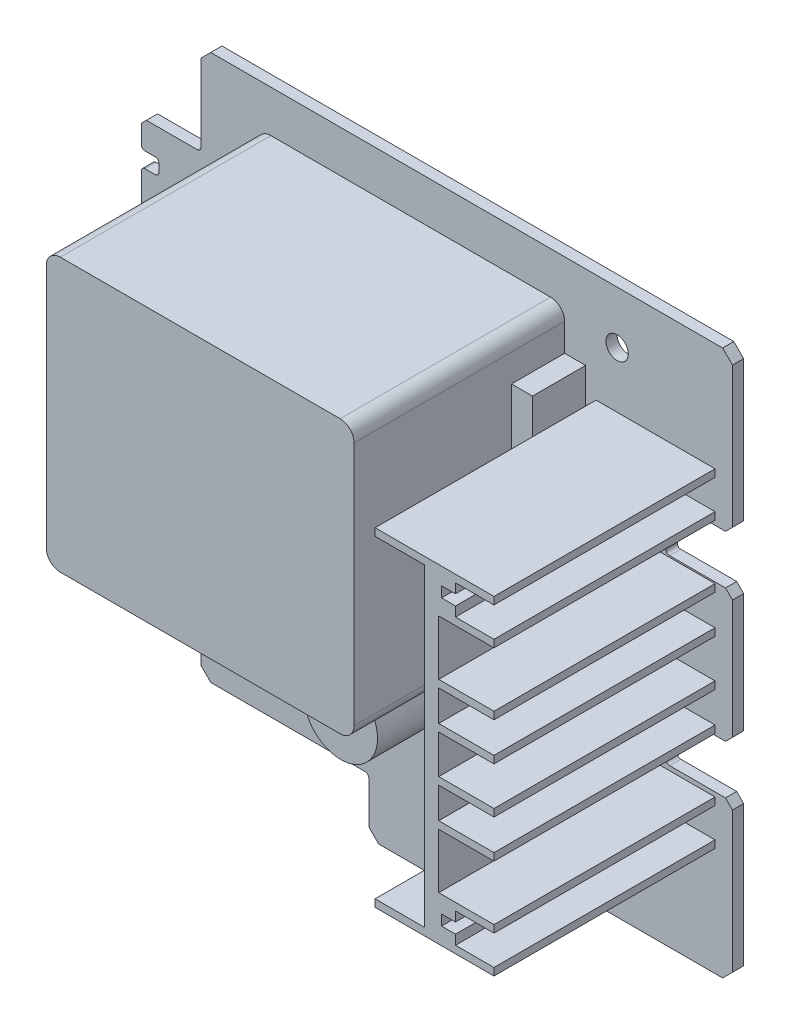
SolidWorks part; units mm, degrees
ref_plane "Front Plane" through (0, 0, 0) normal (0, 0, 1) x (1, 0, 0)
ref_plane "Top Plane" through (0, 0, 0) normal (0, 1, 0) x (1, 0, 0)
ref_plane "Right Plane" through (0, 0, 0) normal (1, 0, 0) x (0, 0, -1)
sketch "Sketch1" plane through (0, 0, 0) normal (0, 0, 1) x (1, 0, 0)
  line L0 (-45.5, -26) -> (-45.5, -13.8)
  line L1 (-45.5, -13.8) -> (-42.5, -13.8)
  line L2 (-42.5, -13.8) -> (-42.5, -8.5)
  line L3 (-42.5, -8.5) -> (-44.5, -8.5)
  line L4 (-44.5, -8.5) -> (-44.5, 8.5)
  line L5 (-44.5, 8.5) -> (-42.5, 8.5)
  line L6 (-42.5, 8.5) -> (-42.5, 13.8)
  line L7 (-42.5, 13.8) -> (-45.5, 13.8)
  line L8 (-45.5, 13.8) -> (-45.5, 19.9)
  line L9 (-45.5, 19.9) -> (-43, 19.9)
  line L10 (-43, 19.9) -> (-43, 22.1)
  line L11 (-43, 22.1) -> (-45.5, 22.1)
  line L12 (-45.5, 22.1) -> (-45.5, 25.2929)
  line L13 (-45.5, 25.2929) -> (-44.7929, 26)
  line L14 (-44.7929, 26) -> (-37, 26)
  line L15 (-37, 26) -> (-37, 37.5858)
  line L16 (-37, 37.5858) -> (-35.5858, 39)
  line L17 (-35.5858, 39) -> (37.5858, 39)
  line L18 (37.5858, 39) -> (39, 37.5858)
  line L19 (39, 37.5858) -> (39, 16.5)
  line L20 (39, 16.5) -> (29.5, 16.5)
  line L21 (29.5, 16.5) -> (29.5, 9.5)
  line L22 (29.5, 9.5) -> (39, 9.5)
  line L23 (39, 9.5) -> (39, -9.5)
  line L24 (39, -9.5) -> (29.5, -9.5)
  line L25 (29.5, -9.5) -> (29.5, -16.5)
  line L26 (29.5, -16.5) -> (39, -16.5)
  line L27 (39, -16.5) -> (39, -37.5858)
  line L28 (39, -37.5858) -> (37.5858, -39)
  line L29 (37.5858, -39) -> (13, -39)
  line L30 (13, -39) -> (13, -45.5858)
  line L31 (13, -45.5858) -> (11.5858, -47)
  line L32 (11.5858, -47) -> (-11.5858, -47)
  line L33 (-11.5858, -47) -> (-13, -45.5858)
  line L34 (-13, -45.5858) -> (-13, -39)
  line L35 (-13, -39) -> (-35.5858, -39)
  line L36 (-35.5858, -39) -> (-37, -37.5858)
  line L37 (-37, -37.5858) -> (-37, -26)
  line L38 (-37, -26) -> (-45.5, -26)
  line L39 (-44.5, 0) -> (0, 0) construction
  line L40 (0, -47) -> (0, 0) construction
  circle A0 centre (-40.5, -21) radius 1.6
  circle A1 centre (22.5, 31.5) radius 1.6
  circle A2 centre (22.5, -31.5) radius 1.6
  dimension "D1" = 3.2
  dimension "D2" = 63
  dimension "D3" = 60
  dimension "D4" = 63
  dimension "D5" = 63
  dimension "D6" = 7.5
  dimension "D7" = 78
  dimension "D8" = 13
  dimension "D9" = 8.5
  dimension "D10" = 86
  dimension "D11" = 5.3
  dimension "D12" = 3
  dimension "D13" = 2.2
  dimension "D14" = 2.5
  dimension "D15" = 58.5
  dimension "D16" = 32.5
  dimension "D17" = 65
  dimension "D18" = 16.9
  dimension "D19" = 25.2
  dimension "D20" = 47.5
  dimension "D21" = 135
  dimension "D22" = 1
  dimension "D23" = 84.5
  dimension "D24" = 135
  dimension "D25" = 2
  dimension "D26" = 8.5
  dimension "D27" = 7
  dimension "D28" = 19
  dimension "D29" = 22.5
  dimension "D30" = 9.5
  dimension "D31" = 2
  dimension "D32" = 135
  dimension "D33" = 135
  dimension "D34" = 135
  dimension "D35" = 5
extrude "Boss-Extrude1" add sketch "Sketch1" along normal blind 1.6
chamfer "Chamfer1" distance 2 angle 45 1 edges at (-45.5, -26, 0.8)
chamfer "Chamfer2" distance 1 angle 45 4 edges at (39, 16.5, 0.8) (39, 9.5, 0.8) (39, -16.5, 0.8) (39, -9.5, 0.8)
fillet "Fillet1" radius 0.5 20 edges at (-45.5, 19.9, 0.8) (-45.5, 22.1, 0.8) (-45.5, 13.8, 0.8) (-44.5, 8.5, 0.8) (-45.5, -13.8, 0.8) (-44.5, -8.5, 0.8) (-37, 26, 0.8) (29.5, 16.5, 0.8) (29.5, 9.5, 0.8) (29.5, -9.5, 0.8) (29.5, -16.5, 0.8) (13, -39, 0.8) (-13, -39, 0.8) (-37, -26, 0.8) (-43, 19.9, 0.8) (-43, 22.1, 0.8) (-42.5, 13.8, 0.8) (-42.5, 8.5, 0.8) (-42.5, -13.8, 0.8) (-42.5, -8.5, 0.8)
sketch "Sketch2" plane through (0, 0, 1.6) normal (0, 0, 1) x (1, 0, 0)
  line L2 (36.5, 17.13) -> (28.6, 17.13)
  line L3 (28.6, 17.13) -> (28.6, 9.28)
  line L4 (28.6, 9.28) -> (36.5, 9.28)
  line L7 (36.5, -9.28) -> (28.6, -9.28)
  line L8 (28.6, -9.28) -> (28.6, -17.13)
  line L9 (28.6, -17.13) -> (36.5, -17.13)
  line L11 (36.5, -23.5) -> (19.5, -23.5)
  line L13 (19.5, 23.5) -> (36.5, 23.5)
  line L18 (39, 17.5) -> (39, 37.5858) construction
  line L19 (15, 27.05) -> (18, 27.05)
  line L20 (-29, 33) -> (15, 33)
  line L21 (-29, 33) -> (-29, -6)
  line L22 (-29, -6) -> (15, -6)
  line L23 (15, 33) -> (15, -6)
  line L24 (18, 27.05) -> (18, -0.05)
  line L25 (18, -0.05) -> (15, -0.05)
  line L26 (18, 13.5) -> (15, 13.5) construction
  line L27 (39, -37.5858) -> (39, -17.5) construction
  line L28 (10.5, -20) -> (15.5, -20)
  line L29 (10.5, -20) -> (10.5, -6)
  line L30 (10.5, -6) -> (15.5, -6)
  line L31 (15.5, -20) -> (15.5, -6)
  line L32 (2.5, -22.5) -> (11.5, -22.5)
  line L33 (2.5, -22.5) -> (2.5, -26.5)
  line L34 (2.5, -26.5) -> (11.5, -26.5)
  line L35 (11.5, -22.5) -> (11.5, -26.5)
  line L36 (-11.5858, -47) -> (11.5858, -47) construction
  line L37 (13.5, -39) -> (37.5858, -39) construction
  line L38 (37.5858, 39) -> (-35.5858, 39) construction
  line L39 (36.5, -22.44) -> (31, -22.44)
  line L40 (31, -22.44) -> (31, -21.065)
  line L41 (31, -21.065) -> (29, -21.065)
  line L42 (29, -21.065) -> (29, -19.565)
  line L43 (29, -19.565) -> (31, -19.565)
  line L44 (31, -19.565) -> (31, -18.19)
  line L45 (31, -18.19) -> (36.5, -18.19)
  line L46 (36.5, -8.22) -> (28.6, -8.22)
  line L47 (28.6, -8.22) -> (28.6, -3.82)
  line L48 (28.6, -3.82) -> (36.5, -3.82)
  line L49 (36.5, -3.82) -> (36.5, -2.76)
  line L50 (36.5, -2.76) -> (28.6, -2.76)
  line L51 (28.6, -2.76) -> (28.6, 2.76)
  line L52 (28.6, 2.76) -> (36.5, 2.76)
  line L53 (36.5, -22.44) -> (36.5, -23.5)
  line L54 (36.5, -18.19) -> (36.5, -17.13)
  line L55 (36.5, -8.22) -> (36.5, -9.28)
  line L56 (36.5, 2.76) -> (36.5, 3.82)
  line L57 (36.5, 3.82) -> (28.6, 3.82)
  line L58 (28.6, 3.82) -> (28.6, 8.22)
  line L59 (28.6, 8.22) -> (36.5, 8.22)
  line L60 (36.5, 8.22) -> (36.5, 9.28)
  line L61 (36.5, 23.5) -> (36.5, 22.44)
  line L62 (36.5, 22.44) -> (31, 22.44)
  line L63 (31, 22.44) -> (31, 21.065)
  line L64 (31, 21.065) -> (29, 21.065)
  line L65 (29, 21.065) -> (29, 19.565)
  line L66 (29, 19.565) -> (31, 19.565)
  line L67 (31, 19.565) -> (31, 18.19)
  line L68 (31, 18.19) -> (36.5, 18.19)
  line L69 (36.5, 18.19) -> (36.5, 17.13)
  line L70 (19.5, 23.5) -> (19.5, 22.44)
  line L71 (19.5, 22.44) -> (26.6, 22.44)
  line L72 (26.6, 22.44) -> (26.6, -22.44)
  line L73 (26.6, -22.44) -> (19.5, -22.44)
  line L74 (19.5, -22.44) -> (19.5, -23.5)
  line L75 (28.6, 0) -> (39, 0) construction
  line L76 (39, -8.5) -> (39, 8.5) construction
  circle A0 centre (3, -14) radius 5.25
  dimension "D8" = 10.5
  dimension "D1" = 47
  dimension "D3" = 17
  dimension "D4" = 44
  dimension "D5" = 39
  dimension "D6" = 27.1
  dimension "D7" = 3
  dimension "D9" = 14
  dimension "D10" = 5
  dimension "D11" = 9
  dimension "D12" = 4
  dimension "D13" = 36
  dimension "D14" = 33
  dimension "D15" = 20.5
  dimension "D16" = 27.5
  dimension "D17" = 19
  dimension "D18" = 23.5
  dimension "D19" = 6
  dimension "D20" = 24
  dimension "D21" = 1.06
  dimension "D22" = 2.5
  dimension "D23" = 4.4
  dimension "D24" = 5.5
  dimension "D25" = 2
  dimension "D26" = 1.5
  dimension "D27" = 2
  dimension "D28" = 7.9
  dimension "D29" = 7.85
  dimension "D30" = 1.375
extrude "transformer1" add sketch "Sketch2" along normal blind 30.1 separate body contours L23 L20 L21 L22 L30 region at (-7, 13.5, 1.6)
extrude "transformer2" add sketch "Sketch2<3>" along normal blind 7.6 contours L24 L26 L23 L25 | L26 L24 L19 L23 region at (16.5, 20.275, 1.6) region at (16.5, 6.725, 1.6)
sketch "Sketch2<3>" plane through (0, 0, 1.6) normal (0, 0, 1) x (1, 0, 0) same geometry as "Sketch2"
sketch "Sketch3" plane through (0, 0, 0) normal (0, 0, -1) x (-1, 0, 0)
  line L0 (-37.5858, 39) -> (35.5858, 39) construction
  line L1 (45.5, 19.4) -> (45.5, 14.3) construction
  circle A0 centre (18.75, 14.5) radius 0.5
  circle A1 centre (18.75, 23.25) radius 0.5
  dimension "D1" = 1
  dimension "D2" = 24.5
  dimension "D3" = 26.75
  dimension "D4" = 15.75
extrude "transformer3" add sketch "Sketch3" along normal blind 2.2 separate body
extrude "cap1" add sketch "Sketch2<4>" along normal blind 20 separate body contours A0 region at (3, -14, 1.6)
sketch "Sketch2<4>" plane through (0, 0, 1.6) normal (0, 0, 1) x (1, 0, 0) same geometry as "Sketch2"
extrude "heatsink" add sketch "Sketch2<5>" along normal blind 31.6 separate body contours L13 L11 L9 L8 L7 L4 L3 L2 region at (32.55, 17.6298, 1.6)
sketch "Sketch2<5>" plane through (0, 0, 1.6) normal (0, 0, 1) x (1, 0, 0) same geometry as "Sketch2"
extrude "resistor" add sketch "Sketch2<6>" along normal blind 8.5 separate body contours L28 L31 L30 L22 L29 region at (13, -13, 1.6)
sketch "Sketch2<6>" plane through (0, 0, 1.6) normal (0, 0, 1) x (1, 0, 0) same geometry as "Sketch2"
extrude "cap2" add sketch "Sketch2<7>" along normal blind 7 separate body contours L35 L32 L33 L34 region at (7, -24.5, 1.6)
sketch "Sketch2<7>" plane through (0, 0, 1.6) normal (0, 0, 1) x (1, 0, 0) same geometry as "Sketch2"
fillet "Fillet2" radius 2 4 edges at (-29, 33, 16.65) (15, 33, 16.65) (15, -6, 16.65) (-29, -6, 16.65)
